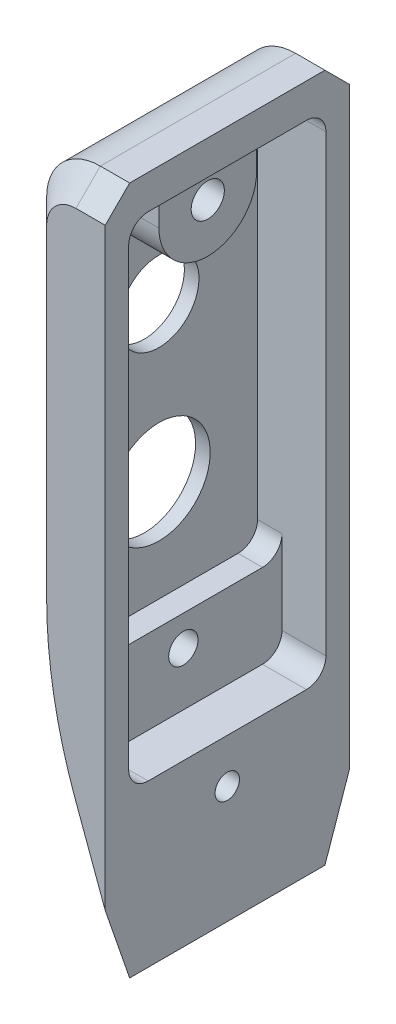
SolidWorks part; units mm, degrees
material "Сплав 2024"
ref_plane "Спереди" through (0, 0, 0) normal (0, 0, 1) x (1, 0, 0)
ref_plane "Сверху" through (0, 0, 0) normal (0, 1, 0) x (1, 0, 0)
ref_plane "Справа" through (0, 0, 0) normal (1, 0, 0) x (0, 0, -1)
sketch "Эскиз1" plane through (0, 0, 0) normal (0, 0, 1) x (1, 0, 0)
  line L0 (0, 0) -> (0, 70.5)
  line L1 (-3, 70.5) -> (0, 70.5)
  line L2 (-8.5, 65) -> (-8.5, 32)
  line L3 (-5.4214, 14.7261) -> (0, 0)
  arc A0 (-3, 70.5) -> (-8.5, 65) centre (-3, 65) ccw
  arc A1 (-8.5, 32) -> (-5.4214, 14.7261) centre (41.5, 32) ccw
  dimension "D2" = 50
  dimension "D5" = 32
  dimension "D1" = 8.5
  dimension "D3" = 70.5
  dimension "D4" = 33
  dimension "D6" = 5.5
extrude "Бобышка-Вытянуть1" add sketch "Эскиз1" along normal blind 25
chamfer "Фаска5" distance 2.5 angle 45 10 edges at (-1.5, 70.5, 0) (-2.7107, 7.3631, 0) (-6.8891, 68.8891, 0) (-7.7243, 23.227, 0) (-8.5, 48.5, 0) (-1.5, 70.5, 25) (-2.7107, 7.3631, 25) (-6.8891, 68.8891, 25) (-7.7243, 23.227, 25) (-8.5, 48.5, 25)
sketch "Эскиз6" plane through (0, 0, 0) normal (1, 0, 0) x (0, 0, -1)
  line L0 (-12.5, 70.5) -> (-12.5, 0) construction
  line L1 (-22.5, 70.5) -> (-2.5, 70.5) construction
  line L2 (-22.5, 0) -> (-2.5, 0) construction
  line L4 (-22.6, 67) -> (-2.4, 67)
  line L5 (-22.6, 67) -> (-22.6, 25.1087)
  line L6 (-22.6, 25.1087) -> (-2.4, 25.1087)
  line L7 (-2.4, 67) -> (-2.4, 25.1087)
  line L8 (-22.6, 67) -> (-2.4, 25.1087) construction
  line L9 (-22.6, 25.1087) -> (-2.4, 67) construction
  point P6 (-12.5, 46.0543)
  dimension "D1" = 20.2
  dimension "D2" = 3.5
  dimension "D3" = 25.1087
extrude "Вырез-Вытянуть2" cut sketch "Эскиз6" against normal offset from surface (7 mm away) 1.5 up to face at (-8.5, 48.5, 12.5)
sketch "Эскиз7" plane through (-8.5, 0, 0) normal (-1, 0, 0) x (0, 0, 1)
  line L0 (12.5, 65) -> (12.5, 25.4737) construction
  line L1 (22.5, 65) -> (2.5, 65) construction
  line L3 (22.5, 0) -> (2.5, 0) construction
  circle A0 centre (12.5, 35.5) radius 5.25
  circle A1 centre (12.5, 51.5) radius 4.1
  dimension "D1" = 10.5
  dimension "D2" = 8.2
  dimension "D3" = 35.5
  dimension "D4" = 16
extrude "Вырез-Вытянуть3" cut sketch "Эскиз7" against normal through all
ref_plane "Плоскость1" through (0, 0, 12.5) normal (0, 0, 1) x (1, 0, 0)
sketch "Эскиз8" plane through (0, 0, 0) normal (1, 0, 0) x (0, 0, -1)
  line L1 (-22.6, 25.1087) -> (-2.4, 25.1087)
  line L2 (-22.6, 25.1087) -> (-22.6, 16.5228)
  line L3 (-22.6, 16.5228) -> (-2.4, 16.5228)
  line L4 (-2.4, 25.1087) -> (-2.4, 16.5228)
extrude "Вырез-Вытянуть4" cut sketch "Эскиз8" against normal offset from surface (4.5 mm away) 2.5 up to face at (-7, 55.6, 12.5)
fillet "Скругление2" radius 2 6 edges at (-2.25, 16.5228, 2.4) (-2.25, 16.5228, 22.6) (-5.75, 25.1087, 22.6) (-5.75, 25.1087, 2.4) (-3.5, 67, 2.4) (-3.5, 67, 22.6)
sketch "Эскиз10" plane through (-8.5, 0, 0) normal (-1, 0, 0) x (0, 0, 1)
  line L0 (12.5, 35.5) -> (12.5, 15.9746) construction
  circle A0 centre (12.5, 22) radius 1.5
  dimension "D1" = 3
  dimension "D2" = 13.5
extrude "Вырез-Вытянуть5" cut sketch "Эскиз10" against normal up to next
sketch "Эскиз11" plane through (0, 0, 0) normal (1, 0, 0) x (0, 0, -1)
  line L0 (-12.5, 16.5228) -> (-12.5, 3.5837) construction
  line L1 (-4.4, 16.5228) -> (-20.6, 16.5228) construction
  line L2 (-22.5, 70.5) -> (-2.5, 70.5) construction
  point P4 (-12.5, 12)
  point P5 (-12.5, 70.5)
  dimension "D1" = 58.5
hole_wizard "Отверстие обработанное метчиком M3x0.51" positions "Эскиз13" profile "Эскиз12" tap size "M3x0.5" standard "Ansi Metric"
sketch "Эскиз13" plane through (0, 0, 0) normal (1, 0, 0) x (0, 0, -1)
  point P0 (-12.5, 12)
sketch "Эскиз12" plane through (0, 12, 12.5) normal (0, 1, 0) x (0, 0, -1)
  line L0 (0, 0) -> (0, 3.7511)
  line L1 (0, 3.7511) -> (1.25, 3)
  line L2 (1.25, 3) -> (1.25, 0)
  line L5 (1.25, 0) -> (0, 0)
  line L10 (0, 3.7511) -> (-1.25, 3) construction
  line L11 (0, -6.35) -> (0, 107.95) construction
  dimension "Диаметр сверла" = 2.5
  dimension "Глубина сверла" = 3
  dimension "Угол заточки сверла" = 118
cosmetic thread "Отверстие резьбы1" parameters "D1"=3, "D2"=3
sketch "Эскиз15" plane through (0, 0, 0) normal (1, 0, 0) x (0, 0, -1)
  line L0 (-12.5, 70.5) -> (-12.5, 67) construction
  line L1 (-22.5, 70.5) -> (-2.5, 70.5) construction
  line L2 (-4.4, 67) -> (-20.6, 67) construction
  point P6 (-12.5, 65.5)
  dimension "D1" = 5
sketch "Эскиз18" plane through (-8.5, 0, 0) normal (-1, 0, 0) x (0, 0, 1)
  line L0 (12.5, 65) -> (12.5, 72.0513) construction
  line L1 (22.5, 65) -> (2.5, 65) construction
  line L2 (22.5, 70.5) -> (2.5, 70.5) construction
  point P4 (12.5, 68)
  dimension "D1" = 2.5
sketch "Эскиз22" plane through (-7, 0, 0) normal (1, 0, 0) x (0, 0, -1)
  line L1 (-12.5, 67) -> (-12.5, 58.1189) construction
  line L2 (-20.6, 67) -> (-4.4, 67) construction
  line L3 (-17.5, 63) -> (-17.5, 67)
  line L4 (-4.4, 67) -> (-20.6, 67) construction
  line L5 (-17.5, 67) -> (-7.5, 67)
  line L6 (-7.5, 67) -> (-7.5, 63)
  arc A0 (-17.5, 63) -> (-7.5, 63) centre (-12.5, 63) ccw
  dimension "D1" = 10
  dimension "D2" = 4
extrude "Бобышка-Вытянуть3" add sketch "Эскиз22" along normal blind 5
fillet "Скругление3" radius 2 2 edges at (-4.5, 67, 7.5) (-4.5, 67, 17.5)
hole_wizard "Цековка для винта с внутренним шестигранником M32" positions "Эскиз24" profile "Эскиз23" counterbore size "M3" standard "Ansi Metric" end condition through all
sketch "Эскиз24" plane through (-8.5, 0, 0) normal (-1, 0, 0) x (0, 0, 1)
  point P0 (12.5, 63)
sketch "Эскиз23" plane through (-8.5, 63, 12.5) normal (0, 1, 0) x (0, 0, 1)
  line L0 (0, 0) -> (0, 8.5)
  line L1 (0, 8.5) -> (1.7, 8.5)
  line L3 (1.7, 8.5) -> (1.7, 2.5)
  line L4 (1.7, 2.5) -> (3.25, 2.5)
  line L5 (3.25, 2.5) -> (3.25, 0)
  line L7 (3.25, 0) -> (0, 0)
  line L11 (0, -6.35) -> (0, 107.95) construction
  dimension "Диаметр сквозного отверстия" = 3.4
  dimension "Глубина сквозного отверстия" = 8.5
  dimension "Диаметр цековки" = 6.5
  dimension "Глубина цековки" = 2.5
sketch "Эскиз25" [suppressed] plane through (0, 0, 25) normal (0, 0, 1) x (1, 0, 0)
  line L1 (0, 70.5) -> (-8.7273, 70.5)
  line L2 (0, 70.5) -> (0, 74.5223)
  line L3 (0, 74.5223) -> (-8.7273, 74.5223)
  line L4 (-8.7273, 70.5) -> (-8.7273, 74.5223)
extrude "Вырез-Вытянуть6" [suppressed] cut sketch "Эскиз25" against normal up to next
equation "\"D3@Эскиз1\"=73.00-2.5"
